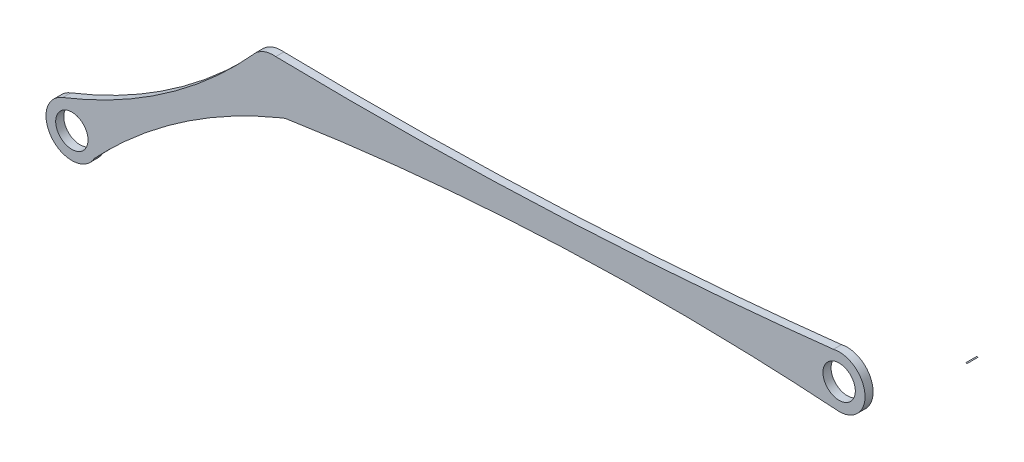
SolidWorks part; units mm, degrees
material "1060 Alloy"
ref_plane "Front Plane" through (0, 0, 0) normal (0, 0, 1) x (1, 0, 0)
ref_plane "Top Plane" through (0, 0, 0) normal (0, 1, 0) x (1, 0, 0)
ref_plane "Right Plane" through (0, 0, 0) normal (1, 0, 0) x (0, 0, -1)
sketch "Sketch1" plane through (0, 0, 0) normal (0, 0, 1) x (1, 0, 0)
  line L0 (0, 0) -> (279.4, 0) construction
  line L1 (7.0023, 16.6052) -> (278.5791, 25.3867)
  line L2 (16.974, -33.8989) -> (280.2209, -25.3867)
  line L3 (0, 0) -> (-97.2876, -81.634) construction
  line L4 (2.6264, -38.9122) -> (-82.1191, -102.0074)
  line L5 (-10.5891, 14.582) -> (-112.4562, -61.2606)
  arc A0 (7.0023, 16.6052) -> (-10.5891, 14.582) centre (0, 0) ccw
  arc A1 (280.2209, -25.3867) -> (278.5791, 25.3867) centre (279.4, 0) ccw
  arc A3 (-112.4562, -61.2606) -> (-82.1191, -102.0074) centre (-97.2876, -81.634) ccw
  arc A4 (0, 18.0212) -> (-10.5891, 14.582) centre (0, 0) ccw
  arc A5 (2.6264, -38.9122) -> (16.974, -33.8989) centre (17.7949, -59.2856) cw
  circle A6 centre (-97.2876, -81.634) radius 7.9375
  circle A7 centre (279.4, 0) radius 7.9375
  point P3 (114.3, 0)
  point P10 (-50.9335, -37.9213)
  dimension "D2" = 127
  dimension "D3" = 50.8
  dimension "D4" = 15.875
  dimension "D8" = 25.4
  dimension "D9" = 25.4
  dimension "D1" = 279.4
  dimension "D6" = 140
  dimension "D7" = 50.8
extrude "Boss-Extrude1" add sketch "Sketch1" along normal blind 3.9688 contours L4 A5 L2 A1 L1 A0 L5 A3 A7 A6 region at (83.2277, -18.6304, 0)
sketch "Sketch2" plane through (0, 0, 3.9688) normal (0, 0, 1) x (1, 0, 0)
  line L0 (16.974, -33.8989) -> (280.2209, -25.3867) construction
  line L1 (7.0023, 16.6052) -> (278.5791, 25.3867) construction
  line L2 (-97.2876, -81.634) -> (1.5952, -12.7) construction
  line L3 (-134.3295, -73.2391) -> (-53.9694, -4.7447)
  line L4 (-93.0845, -119.382) -> (5.3912, -67.5917)
  line L5 (279.4, 0) -> (1.5952, -12.7) construction
  line L6 (280.56, -25.3735) -> (5.3912, -67.5917)
  line L7 (278.24, 25.3735) -> (46.7414, 20.6549)
  arc A0 (-101.7594, -69.7473) -> (-86.2073, -87.8401) centre (-97.2876, -81.634) ccw
  arc A1 (277.6706, -12.5817) -> (276.5811, 12.3832) centre (279.4, 0) ccw
  arc A2 (5.3912, -24.8194) -> (7.3439, -24.0245) centre (1.5952, -12.7) ccw
  arc A3 (16.974, -33.8989) -> (2.6264, -38.9122) centre (17.7949, -59.2856) ccw construction
  arc A4 (2.8221, -0.0594) -> (-8.3044, -4.7447) centre (1.5952, -12.7) ccw
  arc A5 (-134.3295, -73.2391) -> (-93.0845, -119.382) centre (-97.2876, -81.634) ccw
  arc A6 (46.7414, 20.6549) -> (-53.9694, -4.7447) centre (1.5952, -12.7) ccw
  arc A7 (280.56, -25.3735) -> (278.24, 25.3735) centre (279.4, 0) ccw
  arc A8 (46.7414, 20.6549) -> (-30.5051, 33.3466) centre (1.5952, -12.7) ccw
  spline S0 degree 2 poles (7.3439, -24.0245) (-46.6543, -45.771) (-86.2073, -87.8401) knots 0 0 0 1 1 1
  spline S1 degree 2 poles (-102.152, -69.9025) (-47.7798, -48.4603) (-8.3044, -4.7447) knots 0 0 0 1 1 1
  spline S2 degree 2 poles (0, 0) (140.154, -3.0443) (279.4, 12.7) knots 0 0 0 1 1 1
  spline S3 degree 2 poles (7.3439, -24.0245) (142.7973, -3.2601) (279.4, -12.7) knots 0 0 0 1 1 1
  point P4 (-47.8462, -47.167)
  point P20 (9.4165, -35.3073)
  point P35 (140.4976, -6.35)
  line M6 (-82.1191, -102.0074) -> (2.6264, -38.9122)
  arc M7 (2.6264, -38.9122) -> (16.974, -33.8989) centre (17.7949, -59.2856) cw
  line M8 (16.974, -33.8989) -> (280.2209, -25.3867)
  arc M9 (280.2209, -25.3867) -> (278.5791, 25.3867) centre (279.4, 0) ccw
  line M10 (278.5791, 25.3867) -> (7.0023, 16.6052)
  arc M11 (7.0023, 16.6052) -> (-10.5891, 14.582) centre (0, 0) ccw
  line M12 (-10.5891, 14.582) -> (-112.4562, -61.2606)
  arc M13 (-112.4562, -61.2606) -> (-82.1191, -102.0074) centre (-97.2876, -81.634) ccw
  dimension "D1" = 25.4
  dimension "D2" = 25.4
  dimension "D3" = 22.6073
  dimension "D4" = 19.05
  dimension "D5" = 19.05
extrude "Cut-Extrude1" cut sketch "Sketch2" against normal through all contours A7 L7 S3 A2 S0 A0 S1 A4 S2 A1 M9 M10 M11 M12 M13 M6 M7 M8 | L7 A6 L3 A5 L4 L6 M9 M8 M7 M6 M13 M12 M11 M10 region at (21.4845, -36.3339, 3.9688) region at (82.2202, -18.9198, 3.9688)
scale "Scale1" bodies to scale 102 scale about centroid uniform scaling yes scale factor 0.75
